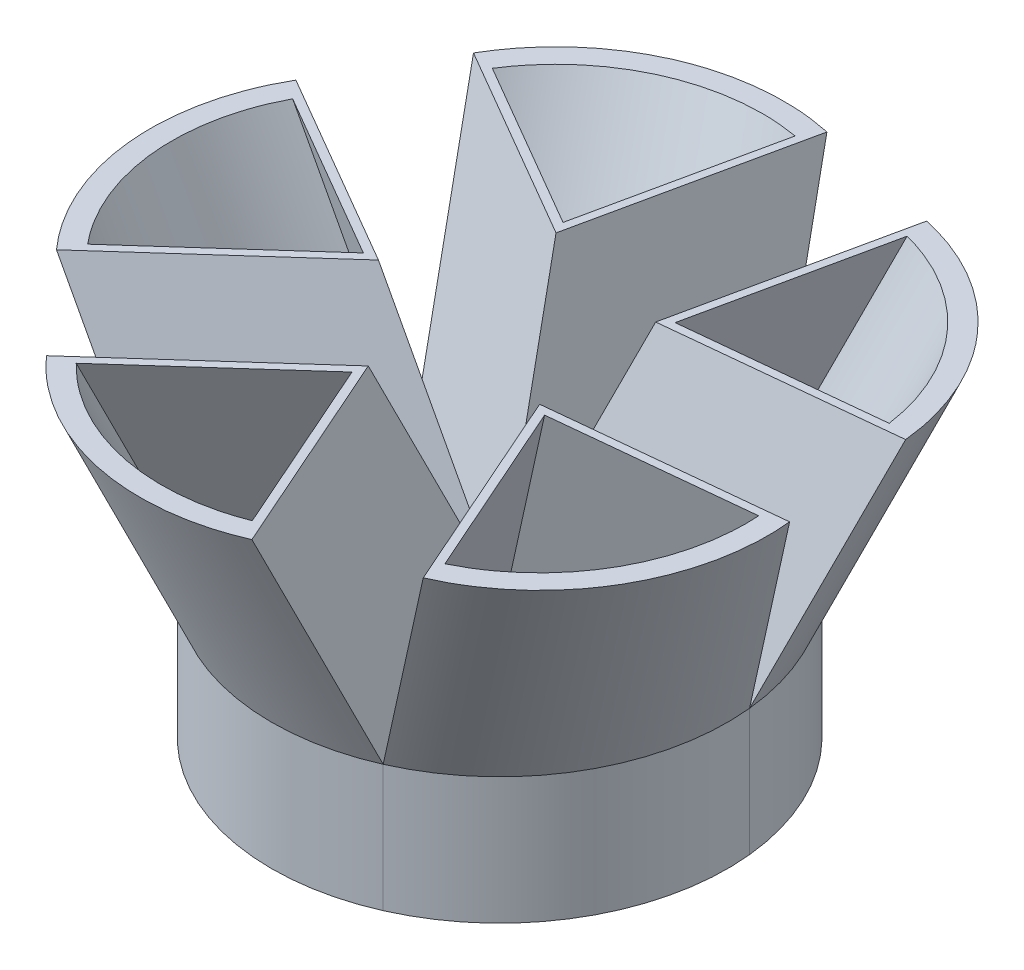
SolidWorks part; units mm, degrees
ref_plane "Front Plane" through (0, 0, 0) normal (0, 0, 1) x (1, 0, 0)
ref_plane "Top Plane" through (0, 0, 0) normal (0, 1, 0) x (1, 0, 0)
ref_plane "Right Plane" through (0, 0, 0) normal (1, 0, 0) x (0, 0, -1)
sketch "Sketch1" plane through (0, 0, 0) normal (0, 1, 0) x (1, 0, 0)
  line L0 (0, 0) -> (-26.7938, -23.9861)
  line L1 (0, 0) -> (14.5324, -32.8946)
  line L2 (0, 0) -> (-0.4567, -2.1186) construction
  line L3 (-0.4567, -2.1186) -> (-23.4067, -22.6637)
  line L4 (-0.4567, -2.1186) -> (11.9909, -30.2941)
  line L5 (-11.4254, -11.938) -> (-12.2751, -10.9888) construction
  line L6 (10.2118, -26.267) -> (11.377, -25.7522) construction
  line L7 (-6.8655, -31.8493) -> (-7.578, -35.1542) construction
  arc A0 (-26.7938, -23.9861) -> (14.5324, -32.8946) centre (0, 0) ccw
  arc A1 (-23.4067, -22.6637) -> (11.9909, -30.2941) centre (0, 0) ccw
  dimension "D1" = 72
extrude "Boss-Extrude1" add sketch "Sketch1" along normal blind 20
ref_plane "Plane1" through (-5.7079, 0, 26.4789) normal (0.2107, 0, -0.9775) x (-0.9775, 0, -0.2107)
ref_axis "Axis2" through (13.4155, 20, 30.6012) along (-0.9775, 0, -0.2107)
ref_plane "Plane4" through (-2.6337, 26.8028, 12.2177) normal (0.0891, -0.9063, -0.4131) x (-0.9775, 0, -0.2107)
ref_plane "Plane5" through (-6.6412, 67.5867, 30.8085) normal (0.0891, -0.9063, -0.4131) x (-0.9775, 0, -0.2107)
sketch "Sketch4" plane through (0, 20, 0) normal (0, 1, 0) x (1, 0, 0)
  line L0 (-0.4567, -2.1186) -> (-23.4067, -22.6637) construction
  line L1 (11.9909, -30.2941) -> (-0.4567, -2.1186) construction
  line L2 (14.5324, -32.8946) -> (0, 0)
  line L3 (0, 0) -> (-26.7938, -23.9861)
  line L4 (14.5324, -32.8946) -> (0, 0)
  line L5 (0, 0) -> (-26.7938, -23.9861)
  line L6 (-0.4567, -2.1186) -> (-23.4067, -22.6637)
  line L7 (11.9909, -30.2941) -> (-0.4567, -2.1186)
  arc A0 (-23.4067, -22.6637) -> (11.9909, -30.2941) centre (0, 0) ccw construction
  arc A1 (-26.7938, -23.9861) -> (14.5324, -32.8946) centre (0, 0) ccw
  arc A2 (-26.7938, -23.9861) -> (14.5324, -32.8946) centre (0, 0) ccw
  arc A3 (-23.4067, -22.6637) -> (11.9909, -30.2941) centre (0, 0) ccw
  dimension "D1" = 0
extrude "Boss-Extrude2" add sketch "Sketch4" along direction (0.0891, -0.9063, -0.4131) on the side of the normal up to surface (56.4475 mm away) up to plane "Plane5"
pattern_circular "CirPattern1" count 5 over 360 about axis through (0, 20, 0) along (0, -1, 0) of "Boss-Extrude1" reverse direction yes
ref_plane "Plane6" through (0, 57.3847, 0) normal (0, 1, 0) x (1, 0, 0)
sketch "Sketch5" plane through (0, 57.3847, 0) normal (0, 1, 0) x (1, 0, 0)
  line L1 (75.6389, -119.3209) -> (-105.1402, -119.3209)
  line L2 (75.6389, -119.3209) -> (75.6389, 101.8929)
  line L3 (75.6389, 101.8929) -> (-105.1402, 101.8929)
  line L4 (-105.1402, -119.3209) -> (-105.1402, 101.8929)
extrude "Cut-Extrude1" cut sketch "Sketch5" along normal through all
